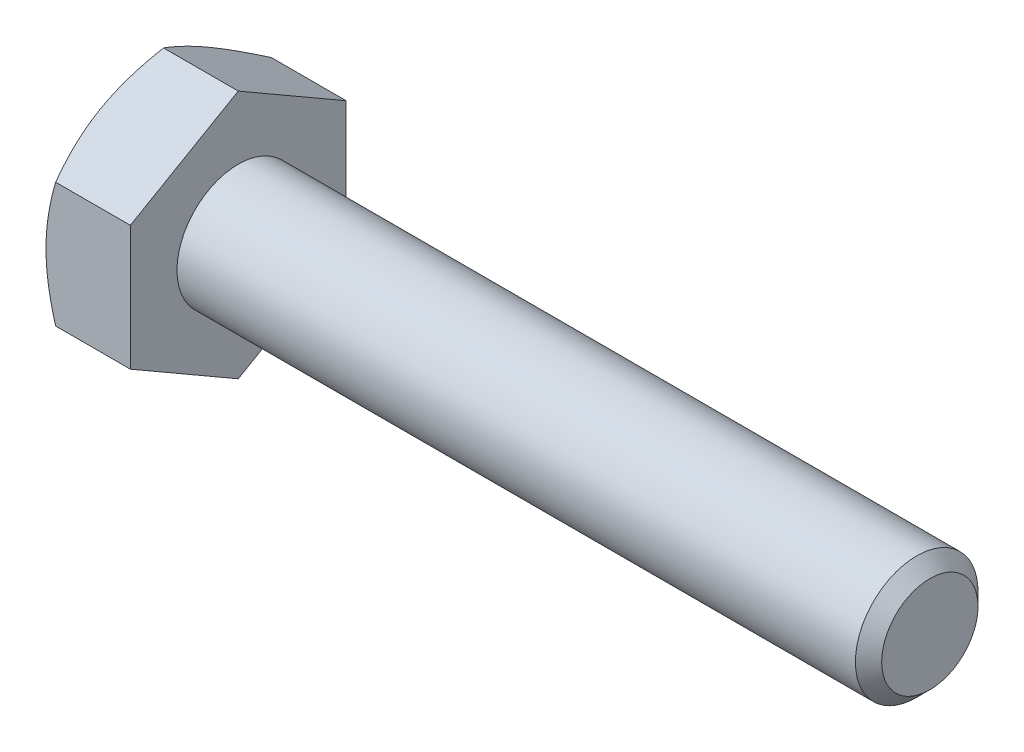
SolidWorks part; units mm, degrees
material "Alloy Steel (SS)"
ref_plane "Front Plane" through (0, 0, 0) normal (0, 0, 1) x (1, 0, 0)
ref_plane "Top Plane" through (0, 0, 0) normal (0, 1, 0) x (1, 0, 0)
ref_plane "Right Plane" through (0, 0, 0) normal (1, 0, 0) x (0, 0, -1)
sketch "Sketch1" plane through (0, 0, 0) normal (0, 0, 1) x (1, 0, 0)
  line L0 (-20.0914, 0) -> (20.0914, 0) construction
  line L1 (20.0914, 3.175) -> (20.0914, -3.175) construction
  line L2 (-15.7226, 5.588) -> (-15.7226, -5.588) construction
  line L3 (-20.0914, 5.588) -> (-20.0914, -5.588) construction
  point P9 (-15.7226, 0)
  point P10 (16.9164, -3.175)
  dimension "Screw Dia" = 6.35
  dimension "Hex" = 11.176
  dimension "Head Ht" = 4.3688
  dimension "Screw Lenght" = 35.814
  dimension "D1" = 3.175
ref_plane "Plane2" through (20.0914, 0, 0) normal (1, 0, 0) x (0, 0, -1)
sketch "Sketch5" plane through (20.0914, 0, 0) normal (1, 0, 0) x (0, 0, -1)
  circle A0 centre (0, 0) radius 3.175
extrude "Boss-Extrude3" add sketch "Sketch5" against normal up to vertex (35.814 mm away) up to point (-15.7226, 0, 0)
sketch "Sketch9" plane through (20.0914, 0, 0) normal (1, 0, 0) x (0, 0, -1)
  circle A1 centre (0, 0) radius 3.175
  circle A2 centre (0, 0) radius 3.175
  dimension "D1" = 0
curve "Helix/Spiral1" [suppressed] pitch 0.9071 height 35.814 turns 39.48 parameters "Pitch"=0.9071
chamfer "Chamfer1" distance 0.6804 angle 45 1 edges at (20.0914, 0, -3.175)
sketch "Sketch10" plane through (0, 0, 0) normal (0, 0, 1) x (1, 0, 0)
  line L0 (19.6945, 3.175) -> (20.0347, 2.5858)
  line L1 (20.0347, 2.5858) -> (20.1481, 2.5858)
  line L2 (20.1481, 2.5858) -> (20.4883, 3.175)
  line L3 (19.6945, 3.175) -> (20.4883, 3.175)
  line L4 (20.0914, 3.175) -> (20.0914, 2.5858) construction
  line L5 (19.8646, 2.8804) -> (20.3182, 2.8804) construction
  dimension "D1" = 60
  dimension "D2" = 0.1134
  dimension "D3" = 0.4536
sweep "Cut-Sweep1" [suppressed] cut profiles "Sketch10" path "Helix/Spiral1"
sketch "Sketch11" plane through (0, 0, 0) normal (0, 0, 1) x (1, 0, 0)
  line L0 (-15.7226, 3.175) -> (-15.7226, 0)
  line L1 (-15.7226, 0) -> (10.0119, 0)
  line L2 (10.0119, 0) -> (8.1788, 3.175)
  line L4 (-15.7226, 3.175) -> (8.1788, 3.175)
  dimension "D1" = 60
  dimension "D2" = 11.9126
revolve "Revolve1" [suppressed] add sketch "Sketch11" angle 360 about L1
sketch "Sketch6" plane through (-15.7226, 0, 0) normal (-1, 0, 0) x (0, 0, 1)
  line L0 (0, 5.588) -> (0, -5.588) construction
  line L1 (5.588, 3.2262) -> (0, 6.4525)
  line L2 (0, 6.4525) -> (-5.588, 3.2262)
  line L3 (-5.588, 3.2262) -> (-5.588, -3.2262)
  line L4 (-5.588, -3.2262) -> (0, -6.4525)
  line L5 (0, -6.4525) -> (5.588, -3.2262)
  line L6 (5.588, -3.2262) -> (5.588, 3.2262)
  circle A0 centre (0, 0) radius 5.588 construction
extrude "Boss-Extrude4" add sketch "Sketch6" along normal up to vertex (4.3688 mm away) up to point (-20.0914, -5.588, 0)
sketch "Sketch8" plane through (-20.0914, 0, 0) normal (-1, 0, 0) x (0, 0, 1)
  circle A0 centre (0, 0) radius 5.588 construction
  circle A1 centre (0, 0) radius 5.588
extrude "Cut-Extrude3" cut sketch "Sketch8" against normal through all draft 60 flip side to cut
sketch "Sketch13" plane through (-20.0914, 0, 0) normal (-1, 0, 0) x (0, 0, 1)
  line L0 (0, 0) -> (-1.8627, 0) construction
  line L1 (-3.7253, -1.8627) -> (-1.8627, -1.8627)
  line L2 (-3.7253, -1.8627) -> (-3.7253, -2.794)
  line L3 (-3.7253, -2.794) -> (-1.8627, -2.794)
  line L4 (-1.8627, -1.8627) -> (-1.8627, -2.794)
  line L5 (-1.8627, 0) -> (-3.7253, 0) construction
  line L6 (-3.7253, 0) -> (-5.588, 0) construction
  line L7 (-1.8627, 0) -> (-1.8627, -1.8627) construction
  line L8 (-3.7253, -1.8627) -> (-3.7253, 0) construction
  line L9 (-2.794, -1.8627) -> (-1.8627, -1.8627) construction
extrude "Cut-Extrude4" [suppressed] cut sketch "Sketch13" against normal blind 0.254
equation "\"D2@Sketch10\" = \"Pitch@Helix/Spiral1\"*.125"
equation "\"D3@Sketch10\" = \"Pitch@Helix/Spiral1\"*.5"
equation "\"D1@Chamfer1\" = \"Pitch@Helix/Spiral1\"*.75"
equation "\"D1@Sketch1\" = \"Pitch@Helix/Spiral1\"*3.5"
